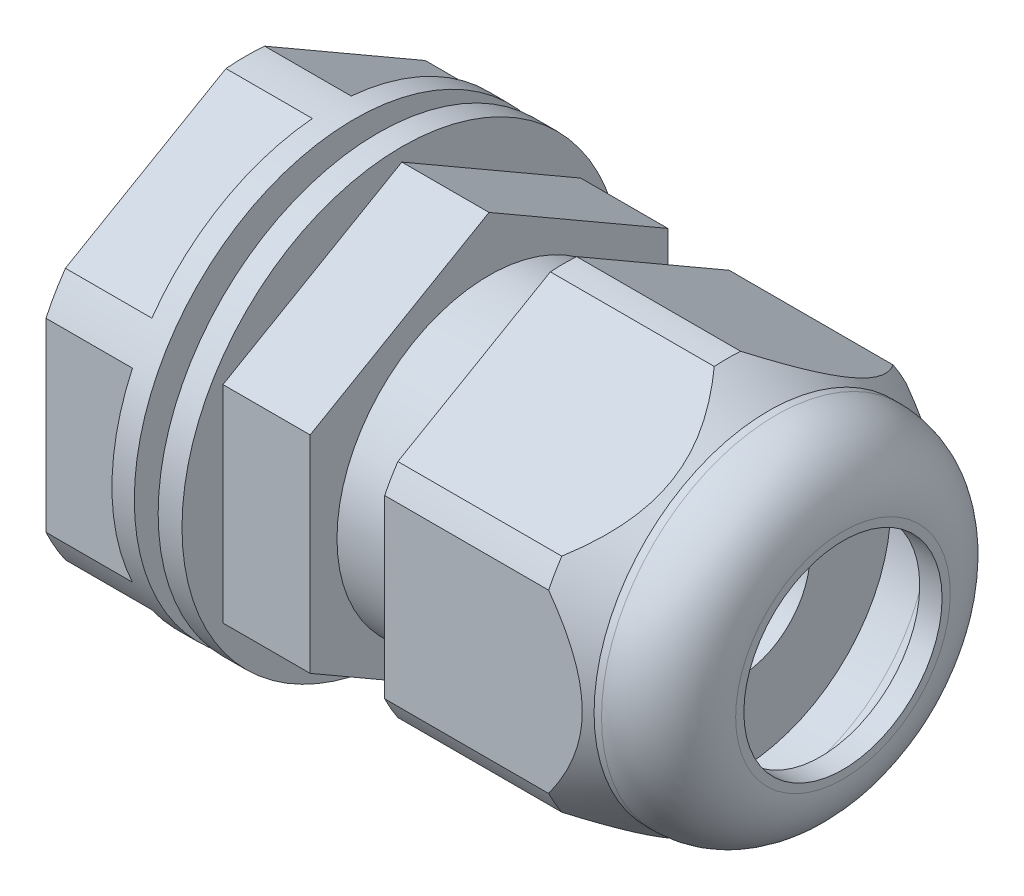
SolidWorks part; units mm, degrees
ref_plane "Front" through (0, 0, 0) normal (0, 0, 1) x (1, 0, 0)
ref_plane "Top" through (0, 0, 0) normal (0, 1, 0) x (1, 0, 0)
ref_plane "Right" through (0, 0, 0) normal (1, 0, 0) x (0, 0, -1)
sketch "Sketch1" plane through (0, 0, 0) normal (1, 0, 0) x (0, 0, -1)
  circle A0 centre (0, 0) radius 10
  dimension "\"c\"D1" = 20
extrude "Boss-Extrude1" add sketch "Sketch1" along normal blind 10.8
sketch "Sketch2" plane through (10.8, 0, 0) normal (1, 0, 0) x (0, 0, -1)
  line L1 (0, -13.8564) -> (12, -6.9282)
  line L2 (12, -6.9282) -> (12, 6.9282)
  line L3 (12, 6.9282) -> (0, 13.8564)
  line L4 (0, 13.8564) -> (-12, 6.9282)
  line L5 (-12, 6.9282) -> (-12, -6.9282)
  line L6 (-12, -6.9282) -> (0, -13.8564)
  circle A0 centre (0, 0) radius 12 construction
  dimension "\"hex\"D1" = 24
extrude "Boss-Extrude2" add sketch "Sketch2" along normal blind 5.85
sketch "Sketch3" plane through (16.65, 0, 0) normal (1, 0, 0) x (0, 0, -1)
  circle A0 centre (0, 0) radius 10.2
  dimension "\"body2\"D1" = 20.4
extrude "Boss-Extrude3" add sketch "Sketch3" along normal offset from surface (16.75 mm away) 33.4 up to face at (0, 0, -10)
sketch "Sketch4" plane through (10.8, 0, 0) normal (-1, 0, 0) x (0, 0, 1)
  circle A0 centre (0, 0) radius 14.75
  dimension "\"gasket diameter\"D1" = 29.5
extrude "Boss-Extrude4" add sketch "Sketch4" along normal blind 1.6
ref_plane "Plane1" through (7.6, 0, 0) normal (-1, 0, 0) x (0, 0, 1)
ref_axis "Axis1" through (7.6, 0, 16.225) along (0, 0, -1)
sketch "Sketch5" plane through (7.6, 0, 0) normal (-1, 0, 0) x (0, 0, 1)
  circle A0 centre (0, 0) radius 14.75
  dimension "\"H\"D1" = 29.5
extrude "Boss-Extrude5" add sketch "Sketch5" along normal blind 7.3
sketch "Sketch6" plane through (0.3, 0, 0) normal (-1, 0, 0) x (0, 0, 1)
  line L1 (0, -15.4441) -> (13.375, -7.7221)
  line L2 (13.375, -7.7221) -> (13.375, 7.7221)
  line L3 (13.375, 7.7221) -> (0, 15.4441)
  line L4 (0, 15.4441) -> (-13.375, 7.7221)
  line L5 (-13.375, 7.7221) -> (-13.375, -7.7221)
  line L6 (-13.375, -7.7221) -> (0, -15.4441)
  circle A0 centre (0, 0) radius 13.375 construction
  circle A1 centre (0, 0) radius 18.375
  dimension "\"NUT DIA\"D1" = 26.75
  dimension "D2" = 5
extrude "Cut-Extrude1" cut sketch "Sketch6" against normal offset from surface (5.8 mm away) 1.5 up to face at (7.6, 0, 14.75)
sketch "Sketch7" plane through (0, 0, 0) normal (-1, 0, 0) x (0, 0, 1)
  circle A0 centre (0, 0) radius 7.5
  dimension "\"B\"D1" = 15
extrude "Cut-Extrude2" cut sketch "Sketch7" against normal offset from surface (21.9 mm away) 11.5 up to face at (33.4, 0, -10.2)
sketch "Sketch8" plane through (33.4, 0, 0) normal (1, 0, 0) x (0, 0, -1)
  circle A0 centre (0, 0) radius 4.8
  dimension "\"A\"D1" = 9.6
extrude "Cut-Extrude3" cut sketch "Sketch8" against normal up to surface (11.5 mm away) up to face at (21.9, 0, -7.5)
sketch "Sketch9" plane through (0, 0, 0) normal (0, 0, 1) x (1, 0, 0)
  line L0 (21.65, 13.375) -> (32.65, 13.375)
  line L1 (32.65, 13.375) -> (35.4, 11.7)
  line L2 (35.4, 11.7) -> (35.9, 11.7)
  line L3 (40.4, 7.2) -> (40.4, 6.65)
  line L4 (21.65, 13.375) -> (21.65, 10.2)
  line L5 (33.4, 10.2) -> (16.65, 10.2) construction
  line L6 (21.65, 10.2) -> (35.9, 10.2)
  line L7 (38.9, 7.2) -> (38.9, 6.65)
  line L8 (38.9, 6.65) -> (40.4, 6.65)
  line L9 (0, 0) -> (59.2195, 0) construction
  line L11 (16.65, 6.9282) -> (16.65, 13.8564) construction
  arc A0 (40.4, 7.2) -> (35.9, 11.7) centre (35.9, 7.2) ccw
  arc A1 (38.9, 7.2) -> (35.9, 10.2) centre (35.9, 7.2) ccw
  dimension "D6" = 4.5
  dimension "\"OD COLLET\"D1" = 26.75
  dimension "\"C_LENGTH\"D2" = 23.75
  dimension "\"ID COLLET\"D3" = 13.3
  dimension "D4" = 13.75
  dimension "D5" = 5
  dimension "\"OD2\"D7" = 23.4
  dimension "D8" = 2.75
  dimension "D10" = 1.5
revolve "Revolve1" add sketch "Sketch9" angle 360 about L9
sketch "Sketch10" plane through (40.4, 0, 0) normal (1, 0, 0) x (0, 0, -1)
  line L1 (12, -6.9282) -> (12, 6.9282)
  line L2 (12, 6.9282) -> (0, 13.8564)
  line L3 (0, 13.8564) -> (-12, 6.9282)
  line L4 (-12, 6.9282) -> (-12, -6.9282)
  line L5 (-12, -6.9282) -> (0, -13.8564)
  line L6 (0, -13.8564) -> (12, -6.9282)
  circle A0 centre (0, 0) radius 12 construction
  circle A1 centre (0, 0) radius 17
  dimension "\"COLLET HEX\"D1" = 24
  dimension "D2" = 5
extrude "Cut-Extrude4" cut sketch "Sketch10" against normal up to surface (18.75 mm away) up to face at (21.65, 0, -10.2)
